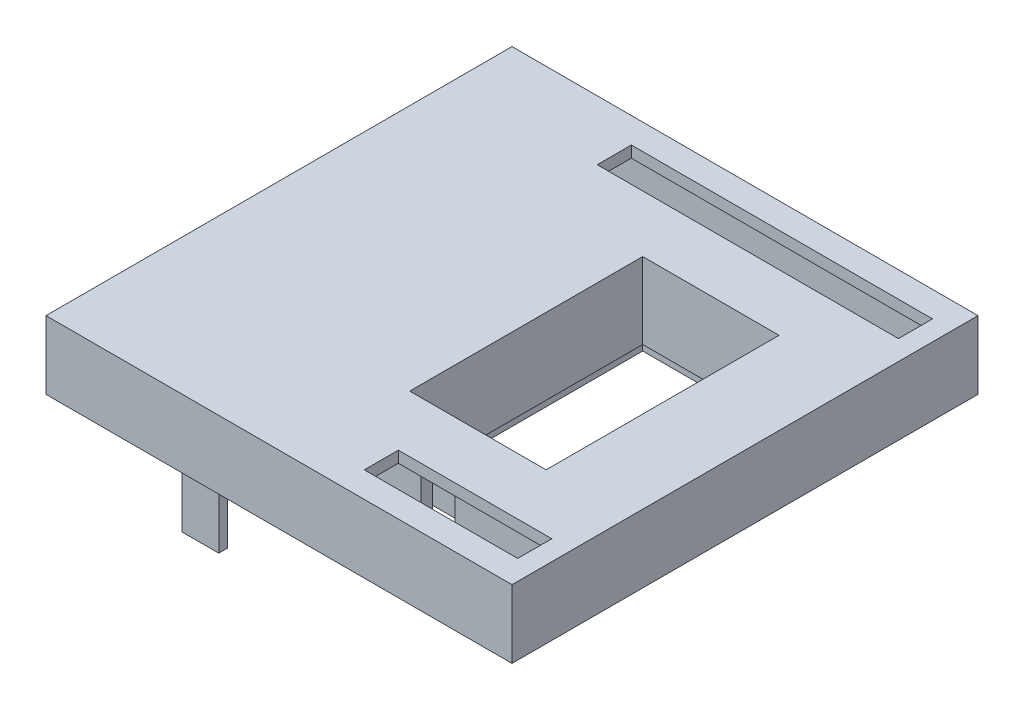
SolidWorks part; units mm, degrees
ref_plane "Front Plane" through (0, 0, 0) normal (0, 0, 1) x (1, 0, 0)
ref_plane "Top Plane" through (0, 0, 0) normal (0, 1, 0) x (1, 0, 0)
ref_plane "Right Plane" through (0, 0, 0) normal (1, 0, 0) x (0, 0, -1)
sketch "Sketch1" plane through (0, 0, 0) normal (0, 1, 0) x (1, 0, 0)
  line L0 (1.5, 1.5) -> (78.5, 1.5) construction
  line L1 (0, 0) -> (80, 0) construction
  line L2 (0, 0) -> (0, 80) construction
  line L3 (0, 80) -> (80, 80) construction
  line L4 (80, 0) -> (80, 80) construction
  line L5 (78.5, 1.5) -> (78.5, 78.5) construction
  line L6 (1.5, 78.5) -> (78.5, 78.5) construction
  line L7 (1.5, 1.5) -> (1.5, 78.5) construction
  dimension "D1" = 1.5
  dimension "D2" = 77
sketch "Sketch5" plane through (0, 0, 0) normal (0, 1, 0) x (1, 0, 0)
  line L0 (0, 0) -> (80, 0) construction
  line L1 (-1, -1) -> (81, -1)
  line L2 (-1, -1) -> (-1, 81)
  line L3 (-1, 81) -> (81, 81)
  line L4 (81, -1) -> (81, 81)
  line L5 (0, 0) -> (0, 80) construction
  line L6 (0, 80) -> (80, 80) construction
  dimension "D1" = 1
  dimension "D2" = 1
  dimension "D3" = 1
extrude "Boss-Extrude3" add sketch "Sketch5" along normal blind 2
sketch "Sketch9" plane through (0, 0, 0) normal (0, -1, 0) x (1, 0, 0)
  line L0 (1.5, -1.5) -> (78.5, -1.5) construction
  line L1 (2.5, -2.5) -> (77.5, -2.5)
  line L2 (2.5, -2.5) -> (2.5, -77.5)
  line L3 (2.5, -77.5) -> (77.5, -77.5)
  line L4 (77.5, -2.5) -> (77.5, -77.5)
  line L5 (1.5, -1.5) -> (1.5, -78.5) construction
  line L7 (1.5, -78.5) -> (78.5, -78.5) construction
  line L9 (78.5, -1.5) -> (78.5, -78.5) construction
  line L11 (81, 1) -> (-1, 1)
  line L12 (81, 1) -> (81, -81)
  line L13 (81, -81) -> (-1, -81)
  line L14 (-1, 1) -> (-1, -81)
  dimension "D1" = 1
  dimension "D2" = 1
  dimension "D3" = 1
  dimension "D4" = 1
extrude "Boss-Extrude5" add sketch "Sketch9" along normal blind 5
sketch "Sketch6" plane through (0, 0, 0) normal (0, -1, 0) x (1, 0, 0)
  line L1 (35.5, -12.5) -> (73.5, -12.5) construction
  line L2 (35.5, -12.5) -> (35.5, -67.5)
  line L3 (35.5, -67.5) -> (73.5, -67.5)
  line L4 (73.5, -12.5) -> (73.5, -67.5)
  line L8 (37.5, -14.5) -> (51.5, -14.5)
  line L9 (71.5, -14.5) -> (71.5, -65.5)
  line L10 (37.5, -65.5) -> (71.5, -65.5)
  line L11 (37.5, -14.5) -> (37.5, -65.5)
  line L12 (77.5, -77.5) -> (77.5, -2.5) construction
  line L13 (2.5, -2.5) -> (2.5, -77.5) construction
  line L14 (57.5, -12.5) -> (57.5, -14.5)
  line L15 (51.5, -12.5) -> (51.5, -14.5)
  line L16 (73.5, -12.5) -> (57.5, -12.5)
  line L17 (51.5, -12.5) -> (35.5, -12.5)
  line L18 (57.5, -14.5) -> (71.5, -14.5)
  line L20 (37.5, -14.5) -> (71.5, -14.5) construction
  point P8 (2.5, -40)
  point P9 (35.5, -40)
  point P18 (54.5, -12.5)
  point P19 (57.5, -13.5)
  dimension "D1" = 4
  dimension "D2" = 34
  dimension "D3" = 51
  dimension "D4" = 3
  dimension "D6" = 6
  dimension "D5" = 2
extrude "Boss-Extrude4" add sketch "Sketch6" along normal offset from surface (17.4 mm away) 12.4 up to face at (40, -5, -40) offset beyond the face yes
sketch "Sketch7" plane through (0, 0, 0) normal (0, -1, 0) x (1, 0, 0)
  line L0 (51.5, -14.5) -> (37.5, -14.5) construction
  line L1 (42.5, -19.5) -> (66.5, -19.5)
  line L2 (42.5, -19.5) -> (42.5, -60.5)
  line L3 (42.5, -60.5) -> (66.5, -60.5)
  line L4 (66.5, -19.5) -> (66.5, -60.5)
  line L5 (37.5, -14.5) -> (37.5, -65.5) construction
  line L6 (37.5, -65.5) -> (71.5, -65.5) construction
  line L7 (71.5, -65.5) -> (71.5, -14.5) construction
  line L8 (78.5, -1.5) -> (78.5, -78.5) construction
  line L9 (77.5, -3.5) -> (50.5, -3.5)
  line L10 (77.5, -3.5) -> (77.5, -9.5)
  line L11 (77.5, -9.5) -> (50.5, -9.5)
  line L12 (50.5, -3.5) -> (50.5, -9.5)
  line L13 (24.5, -76.5) -> (77.5, -76.5)
  line L14 (24.5, -76.5) -> (24.5, -70.5)
  line L15 (24.5, -70.5) -> (77.5, -70.5)
  line L16 (77.5, -76.5) -> (77.5, -70.5)
  line L17 (1.5, -78.5) -> (78.5, -78.5) construction
  line L18 (1.5, -1.5) -> (78.5, -1.5) construction
  dimension "D1" = 5
  dimension "D2" = 5
  dimension "D3" = 5
  dimension "D4" = 5
  dimension "D5" = 1
  dimension "D6" = 2
  dimension "D7" = 8
  dimension "D8" = 1
  dimension "D9" = 2
  dimension "D10" = 8
  dimension "D11" = 28
  dimension "D12" = 54
extrude "Cut-Extrude1" cut sketch "Sketch7" against normal up to surface (2 mm away) up to face at (40, 2, -40)
sketch "Sketch10" plane through (0, -5, 0) normal (0, -1, 0) x (1, 0, 0)
  line L1 (21.9, 0) -> (28.4, 0)
  line L2 (21.9, 0) -> (21.9, -1.5)
  line L3 (21.9, -1.5) -> (28.4, -1.5)
  line L4 (28.4, 0) -> (28.4, -1.5)
  line L6 (1.5, -1.5) -> (1.5, -78.5) construction
  line L7 (0, 0) -> (80, 0) construction
  line L8 (1.5, -1.5) -> (78.5, -1.5) construction
  point P4 (0, 0)
  point P10 (0, 0)
  dimension "D1" = 20.4
  dimension "D2" = 6.5
extrude "Boss-Extrude6" add sketch "Sketch10" along normal blind 15
sketch "Sketch11" plane through (0, -5, 0) normal (0, -1, 0) x (-1, 0, 0)
  line L0 (1, -1) -> (1, 81) construction
  line L1 (-2.5, 77.5) -> (-77.5, 77.5)
  line L2 (-2.5, 77.5) -> (-2.5, 2.5)
  line L3 (-2.5, 2.5) -> (-77.5, 2.5)
  line L4 (-77.5, 77.5) -> (-77.5, 2.5)
  line L5 (-78.5, 1.5) -> (-1.5, 1.5)
  line L6 (-78.5, 1.5) -> (-78.5, 78.5)
  line L7 (-78.5, 78.5) -> (-1.5, 78.5)
  line L8 (-1.5, 1.5) -> (-1.5, 78.5)
  line L9 (0, 80) -> (-80, 80)
  line L10 (0, 80) -> (0, 0)
  line L11 (0, 0) -> (-80, 0)
  line L12 (-80, 80) -> (-80, 0)
  line L13 (-81, -1) -> (1, -1)
  line L14 (-81, -1) -> (-81, 81.0483)
  line L15 (-81, 81.0483) -> (1, 81.0483)
  line L16 (1, -1) -> (1, 81.0483)
  line M13 (-2.5, 77.5) -> (-2.5, 2.5)
  line M14 (-2.5, 2.5) -> (-77.5, 2.5)
  line M15 (-77.5, 2.5) -> (-77.5, 77.5)
  line M16 (-77.5, 77.5) -> (-2.5, 77.5)
  line M17 (-81, 81) -> (-81, -1)
  line M18 (-81, -1) -> (1, -1)
  line M19 (1, -1) -> (1, 81)
  line M20 (1, 81) -> (-81, 81)
  line M22 (-21.9, 0) -> (-28.4, 0)
  line M24 (-28.4, 1.5) -> (-21.9, 1.5)
extrude "Boss-Extrude7" add sketch "Sketch11" along normal blind 5 contours L12 L9 L10 L11 M20 M17 M18 M19 M24 | L5 L8 L7 L6 M22 M16 M13 M14 M15 region at (78.3911, -5, -40) region at (80.884, -5, -40)
sketch "Sketch12" plane through (0, 0, 0) normal (0, -1, 0) x (1, 0, 0)
  line L0 (68.5, -17.5) -> (40.5, -17.5)
  line L5 (66.5, -19.5) -> (42.5, -19.5)
  line L6 (66.5, -19.5) -> (66.5, -60.5)
  line L7 (66.5, -60.5) -> (42.5, -60.5)
  line L8 (42.5, -19.5) -> (42.5, -60.5)
  line L9 (40.5, -17.5) -> (40.5, -62.5)
  line L10 (68.5, -62.5) -> (40.5, -62.5)
  line L11 (68.5, -17.5) -> (68.5, -62.5)
  dimension "D1" = 2
extrude "Boss-Extrude8" add sketch "Sketch12" along normal offset from surface (11.4 mm away) 6 up to face at (54.5, -17.4, -31.1667)
